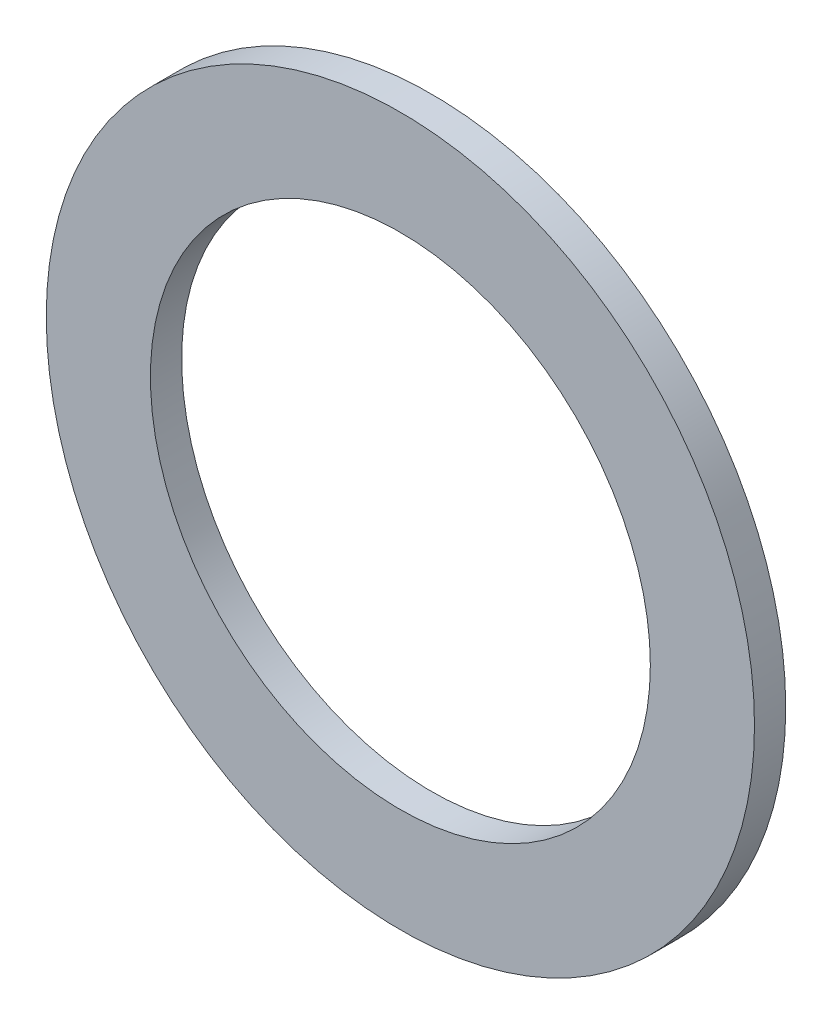
SolidWorks part; units mm, degrees
ref_plane "Спереди" through (0, 0, 0) normal (0, 0, 1) x (1, 0, 0)
ref_plane "Сверху" through (0, 0, 0) normal (0, 1, 0) x (1, 0, 0)
ref_plane "Справа" through (0, 0, 0) normal (1, 0, 0) x (0, 0, -1)
sketch "Эскиз1" plane through (0, 0, 0) normal (0, 0, 1) x (1, 0, 0)
  circle A0 centre (0, 0) radius 12
extrude "Вытянуть-Тонкостенный1" add sketch "Эскиз1" along normal blind 1.5 thin thin type one direction wall 5
